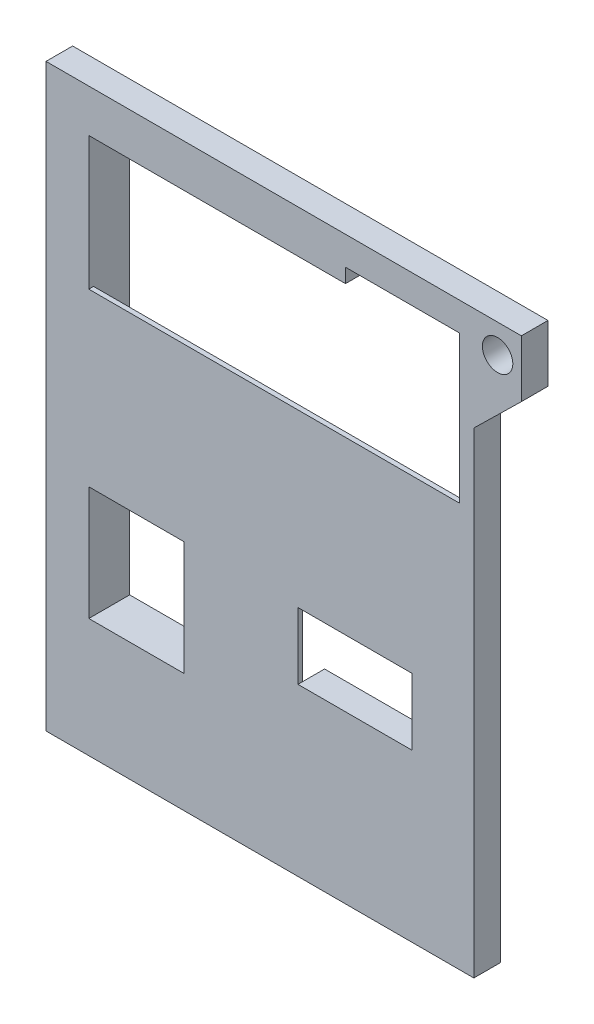
SolidWorks part; units mm, degrees
ref_plane "前视基准面" through (0, 0, 0) normal (0, 0, 1) x (1, 0, 0)
ref_plane "上视基准面" through (0, 0, 0) normal (0, 1, 0) x (1, 0, 0)
ref_plane "右视基准面" through (0, 0, 0) normal (1, 0, 0) x (0, 0, -1)
sketch "草图1" plane through (0, 0, 0) normal (0, 0, 1) x (1, 0, 0)
  line L0 (22.5, 30.5) -> (-22.5, 30.5)
  line L1 (21, -29) -> (-20.5, -29)
  line L2 (21, -29) -> (21, 29)
  line L3 (21, 29) -> (-20.5, 29)
  line L5 (21, -29) -> (-20.5, 28.3095) construction
  line L6 (21, 29) -> (4.2304, 5.842) construction
  line L7 (-22.5, -30.5) -> (-22.5, 30.5)
  line L8 (22.5, -30.5) -> (-22.5, -30.5)
  line L9 (22.5, -30.5) -> (22.5, 30.5)
  line L10 (-18, 12) -> (21, 12)
  line L11 (21, 29) -> (-18, 29)
  line L12 (21, 29) -> (21, -18)
  line L13 (21, -18) -> (-18, -18)
  line L14 (-18, 29) -> (-18, -18)
  line L15 (-2, -18) -> (4, -18)
  line L16 (-2, -18) -> (-2, -11)
  line L17 (-2, -11) -> (4, -11)
  line L18 (4, -18) -> (4, -11)
  line L19 (16, -18) -> (16, -6)
  line L20 (-18, 27.5) -> (21, 27.5)
  line L21 (0, 0) -> (-20.5, -28.3095) construction
  line L22 (-18, 26) -> (9, 26)
  line L23 (16, -6) -> (-18, -6)
  line L24 (16, -9.279) -> (21, -9.279)
  line L25 (-8, -18) -> (-8, -6)
  line L26 (9, 26) -> (9, 27.5)
  line L27 (4, -6) -> (4, -18)
  line L28 (4, -13) -> (16, -13)
  line L29 (-20.5, 29) -> (-20.5, -29)
  line L30 (21, -29) -> (-21, -29) construction
  line L31 (21, 29) -> (-21, 29) construction
  line L33 (-21, -29) -> (-21, 29) construction
  line L34 (22.5, 30.5) -> (27.5, 30.5)
  line L35 (27.5, 30.5) -> (27.5, 24.5)
  line L36 (27.5, 24.5) -> (22.5, 19.601)
  circle A0 centre (1.5, -15) radius 1.6
  circle A1 centre (25, 27.5) radius 1.6
  point P0 (0, 0)
  dimension "D9" = 3
  dimension "D10" = 3.2
  dimension "D23" = 3
  dimension "D4" = 39
  dimension "D5" = 47
  dimension "D6" = 17
  dimension "D7" = 23
  dimension "D8" = 7
  dimension "D11" = 19.5
  dimension "D12" = 30
  dimension "D13" = 12
  dimension "D14" = 1.5
  dimension "D15" = 1.5
  dimension "D16" = 5
  dimension "D17" = 5
  dimension "D18" = 10
  dimension "D19" = 22
  dimension "D20" = 5
  dimension "D21" = 6
  dimension "D22" = 7
  dimension "D24" = 2.5
  dimension "D3" = 1.5
extrude "凸台-拉伸7" add sketch "草图1" against normal blind 2.8 contours L8 L9 L0 L7 L1 L3 L12 L2 | L24 L19 L13 L2 | L22 L26 L20 L14 | L14 L20 L12 L3 | L28 L27 L13 L19 | L36 L35 L34 L9 A1 region at (21.742, 25.0505, 0) region at (24.7016, 25.8411, 0) region at (18.5, -13.6395, 0) region at (10, -15.5, 0) region at (1.5, 28.25, 0) region at (-4.5, 26.75, 0)
extrude "凸台-拉伸8" add sketch "草图1<11>" against normal blind 0.5 contours L8 L9 L0 L7 L1 L3 L2 | L19 L24 L12 L10 L14 L23 | L27 L23 L25 L13 L16 L17 L18 | L13 L18 L27 L17 L16 A0 | A0 region at (21.742, 25.0505, 0) region at (1.888, 2.7572, 0) region at (1, -17.9078, 0) region at (-3.2353, -10.9706, 0)
sketch "草图1<11>" plane through (0, 0, 0) normal (0, 0, 1) x (1, 0, 0) same geometry as "草图1"
extrude "凸台-拉伸9" add sketch "草图1<12>" against normal blind 4.3 contours L14 L3 L1 L2 L13 region at (0.25, -28.2868, 0)
sketch "草图1<12>" plane through (0, 0, 0) normal (0, 0, 1) x (1, 0, 0) same geometry as "草图1"
